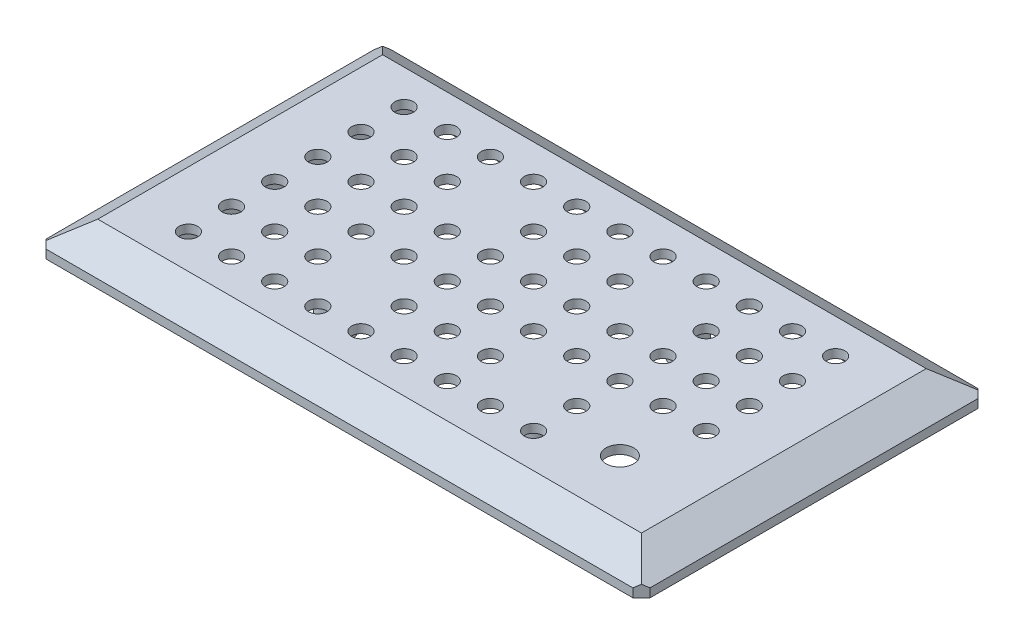
SolidWorks part; units mm, degrees
other "Markierung1"
sketch "Skizze3" plane through (70, 7.0001, 40) normal (0.1525, 0.9868, 0.0548) x (-0.3361, 0.104, -0.9361)
ref_plane "Front Plane" through (0, 0, 0) normal (0, 0, 1) x (1, 0, 0)
ref_plane "Top Plane" through (0, 0, 0) normal (0, 1, 0) x (1, 0, 0)
ref_plane "Right Plane" through (0, 0, 0) normal (1, 0, 0) x (0, 0, -1)
sketch "Sketch1" plane through (0, 0, 0) normal (0, 1, 0) x (1, 0, 0)
  line L1 (-70, -40) -> (70, -40)
  line L2 (-70, -40) -> (-70, 40)
  line L3 (-70, 40) -> (70, 40)
  line L4 (70, -40) -> (70, 40)
  line L5 (-70, -40) -> (70, 40) construction
  line L6 (-70, 40) -> (70, -40) construction
  point P0 (0, 0)
  dimension "D1" = 140
  dimension "D2" = 80
extrude "Boss-Extrude1" add sketch "Sketch1" along normal blind 2
sketch "Sketch2" plane through (0, 2, 0) normal (0, 1, 0) x (1, 0, 0)
  line L4 (70, -40) -> (70, 40)
  line L5 (70, 40) -> (-70, 40)
  line L6 (-70, 40) -> (-70, -40)
  line L7 (-70, -40) -> (70, -40)
  line L8 (70, -40) -> (70, 40)
  line L9 (70, 40) -> (-70, 40)
  line L10 (-70, 40) -> (-70, -40)
  line L11 (-70, -40) -> (70, -40)
  dimension "D1" = 0
ref_plane "Plane1" through (0, 7, 0) normal (0, 1, 0) x (1, 0, 0)
sketch "Sketch3" plane through (0, 7, 0) normal (0, 1, 0) x (1, 0, 0)
  line L0 (-70, 40) -> (-70, -40) construction
  line L1 (-63, -33) -> (63, -33)
  line L2 (-63, -33) -> (-63, 33)
  line L3 (-63, 33) -> (63, 33)
  line L4 (63, -33) -> (63, 33)
  line L5 (-63, -33) -> (63, 33) construction
  line L6 (-63, 33) -> (63, -33) construction
  line L7 (70, 40) -> (-70, 40) construction
  point P0 (0, 0)
  dimension "D1" = 7
  dimension "D2" = 7
loft "Loft1" add profiles "Sketch3", "Sketch2" connector at (-63, 7, 33) connector at (-70, 2, 40)
chamfer "Chamfer2" distance 2 angle 45 4 edges at (70, 1, 40) (70, 1, -40) (-70, 1, -40) (-70, 1, 40)
sketch "Sketch4" plane through (0, 0, 0) normal (0, -1, 0) x (1, 0, 0)
  line L0 (-70, -38) -> (-70, 38) construction
  line L1 (-62.9, 15) -> (-54.9, 15)
  line L2 (-62.9, 15) -> (-62.9, 25)
  line L3 (-62.9, 25) -> (-54.9, 25)
  line L4 (-54.9, 15) -> (-54.9, 25)
  line L5 (-62.9, 15) -> (-54.9, 25) construction
  line L6 (-62.9, 25) -> (-54.9, 15) construction
  line L7 (-70, 0) -> (70, 0) construction
  line L8 (70, 38) -> (70, -38) construction
  line L9 (0, 40) -> (0, -40) construction
  line L10 (-68, 40) -> (68, 40) construction
  line L11 (68, -40) -> (-68, -40) construction
  line L12 (-62.9, -25) -> (-54.9, -15) construction
  line L13 (-62.9, -15) -> (-54.9, -25) construction
  line L14 (-54.9, -15) -> (-54.9, -25)
  line L15 (-62.9, -25) -> (-54.9, -25)
  line L16 (-62.9, -15) -> (-62.9, -25)
  line L17 (-62.9, -15) -> (-54.9, -15)
  line L18 (62.9, -15) -> (54.9, -25) construction
  line L19 (62.9, -25) -> (54.9, -15) construction
  line L20 (62.9, 25) -> (54.9, 15) construction
  line L21 (62.9, 15) -> (54.9, 25) construction
  line L22 (62.9, -15) -> (54.9, -15)
  line L23 (62.9, -15) -> (62.9, -25)
  line L24 (62.9, -25) -> (54.9, -25)
  line L25 (54.9, -15) -> (54.9, -25)
  line L26 (54.9, 15) -> (54.9, 25)
  line L27 (62.9, 25) -> (54.9, 25)
  line L28 (62.9, 15) -> (62.9, 25)
  line L29 (62.9, 15) -> (54.9, 15)
  point P0 (-58.9, 20)
  point P21 (-58.9, -20)
  point P30 (58.9, -20)
  point P31 (58.9, 20)
  dimension "D1" = 10
  dimension "D2" = 7.1
  dimension "D3" = 8
  dimension "D4" = 40
extrude "Boss-Extrude2" add sketch "Sketch4" along normal blind 7
sketch "Sketch5" plane through (-62.9, 0, 0) normal (-1, 0, 0) x (0, 0, 1)
  line L0 (-15, 0) -> (-25, -7) construction
  line L1 (0, 0) -> (0, 50000) construction
  circle A0 centre (-20, -3.5) radius 2.05
  circle A1 centre (20, -3.5) radius 2.05
  dimension "D1" = 4.1
extrude "Cut-Extrude1" cut sketch "Sketch5" against normal through all
sketch "Sketch6" plane through (0, 0, 0) normal (0, -1, 0) x (1, 0, 0)
  line L0 (54.9, 25) -> (54.9, 15) construction
  line L1 (-53.9, -32) -> (53.9, -32)
  line L2 (-53.9, -32) -> (-53.9, 32)
  line L3 (-53.9, 32) -> (53.9, 32)
  line L4 (53.9, -32) -> (53.9, 32)
  line L5 (-53.9, -32) -> (53.9, 32) construction
  line L6 (-53.9, 32) -> (53.9, -32) construction
  line L8 (-63, 33) -> (63, 33) construction
  point P0 (0, 0)
  dimension "D1" = 1
  dimension "D2" = 1
extrude "Cut-Extrude2" cut sketch "Sketch6" against normal offset from surface (5 mm away) 2 up to face at (0, 7, 0)
sketch "Skizze1" plane through (0, 7, 0) normal (0, 1, 0) x (1, 0, 0)
  line L0 (-53.9, 0) -> (53.9, 0) construction
  line L1 (0, -32) -> (0, 32) construction
  line L2 (-50, -25) -> (50, 25) construction
  line L4 (63, -33) -> (63, 33)
  line L5 (63, 33) -> (-63, 33)
  line L6 (-63, 33) -> (-63, -33)
  line L7 (-63, -33) -> (63, -33)
  line L8 (63, -33) -> (63, 33) construction
  line L9 (63, 33) -> (-63, 33) construction
  line L10 (-63, 33) -> (-63, -33) construction
  line L11 (-63, -33) -> (63, -33) construction
  line L12 (53.9, -32) -> (53.9, 32)
  line L13 (-53.9, -32) -> (53.9, -32)
  line L14 (-53.9, 32) -> (-53.9, -32)
  line L15 (53.9, 32) -> (-53.9, 32)
  line L16 (53.9, -32) -> (53.9, 32) construction
  line L17 (-53.9, -32) -> (53.9, -32) construction
  line L18 (-53.9, 32) -> (-53.9, -32) construction
  line L19 (53.9, 32) -> (-53.9, 32) construction
  circle A0 centre (-50, -25) radius 2.15
  circle A1 centre (-40, -25) radius 2.15
  circle A2 centre (-30, -25) radius 2.15
  circle A3 centre (-20, -25) radius 2.15
  circle A4 centre (-10, -25) radius 2.15
  circle A5 centre (0, -25) radius 2.15
  circle A6 centre (10, -25) radius 2.15
  circle A7 centre (20, -25) radius 2.15
  circle A8 centre (30, -25) radius 2.15
  circle A9 centre (40, -25) radius 2.15
  circle A10 centre (50, -25) radius 2.15
  circle A11 centre (-40, -15) radius 2.15
  circle A12 centre (-30, -15) radius 2.15
  circle A13 centre (-20, -15) radius 2.15
  circle A14 centre (-10, -15) radius 2.15
  circle A15 centre (0, -15) radius 2.15
  circle A16 centre (10, -15) radius 2.15
  circle A17 centre (20, -15) radius 2.15
  circle A18 centre (30, -15) radius 2.15
  circle A19 centre (40, -15) radius 2.15
  circle A20 centre (50, -15) radius 2.15
  circle A21 centre (-40, -5) radius 2.15
  circle A22 centre (-30, -5) radius 2.15
  circle A23 centre (-20, -5) radius 2.15
  circle A24 centre (-10, -5) radius 2.15
  circle A25 centre (0, -5) radius 2.15
  circle A26 centre (10, -5) radius 2.15
  circle A27 centre (20, -5) radius 2.15
  circle A28 centre (30, -5) radius 2.15
  circle A29 centre (40, -5) radius 2.15
  circle A30 centre (50, -5) radius 2.15
  circle A31 centre (-40, 5) radius 2.15
  circle A32 centre (-30, 5) radius 2.15
  circle A33 centre (-20, 5) radius 2.15
  circle A34 centre (-10, 5) radius 2.15
  circle A35 centre (0, 5) radius 2.15
  circle A36 centre (10, 5) radius 2.15
  circle A37 centre (20, 5) radius 2.15
  circle A38 centre (30, 5) radius 2.15
  circle A39 centre (40, 5) radius 2.15
  circle A40 centre (50, 5) radius 2.15
  circle A41 centre (-40, 15) radius 2.15
  circle A42 centre (-30, 15) radius 2.15
  circle A43 centre (-20, 15) radius 2.15
  circle A44 centre (-10, 15) radius 2.15
  circle A45 centre (0, 15) radius 2.15
  circle A46 centre (10, 15) radius 2.15
  circle A47 centre (20, 15) radius 2.15
  circle A48 centre (30, 15) radius 2.15
  circle A49 centre (40, 15) radius 2.15
  circle A50 centre (50, 15) radius 2.15
  circle A51 centre (-40, 25) radius 2.15
  circle A52 centre (-30, 25) radius 2.15
  circle A53 centre (-20, 25) radius 2.15
  circle A54 centre (-10, 25) radius 2.15
  circle A55 centre (0, 25) radius 2.15
  circle A56 centre (10, 25) radius 2.15
  circle A57 centre (20, 25) radius 2.15
  circle A58 centre (30, 25) radius 2.15
  circle A59 centre (40, 25) radius 2.15
  circle A60 centre (50, 25) radius 2.15
  circle A61 centre (-50, -15) radius 2.15
  circle A62 centre (-50, -5) radius 2.15
  circle A63 centre (-50, 5) radius 2.15
  circle A64 centre (-50, 15) radius 2.15
  circle A65 centre (-50, 25) radius 2.15
  point P14 (0, 0)
  point P15 (0, 0)
  point P16 (0, 0)
  point P18 (0, 0)
  dimension "D3" = 11
  dimension "D5" = 4.3
  dimension "D1" = 0
  dimension "D2" = 0
  dimension "D4" = 6
extrude "Schnitt-Linear austragen2" cut sketch "Skizze1" against normal blind 10
sketch "Skizze2" plane through (0, 7, 0) normal (0, 1, 0) x (1, 0, 0)
  line L1 (37.85, -27.15) -> (52.15, -27.15)
  line L2 (37.85, -27.15) -> (37.85, -12.85)
  line L3 (37.85, -12.85) -> (52.15, -12.85)
  line L4 (52.15, -27.15) -> (52.15, -12.85)
  line L5 (37.85, -27.15) -> (52.15, -12.85) construction
  line L6 (37.85, -12.85) -> (52.15, -27.15) construction
  circle A0 centre (40, -25) radius 2.15 construction
  circle A1 centre (50, -25) radius 2.15 construction
  circle A2 centre (50, -15) radius 2.15 construction
  circle A3 centre (45, -20) radius 3.2
  point P0 (45, -20)
  dimension "D1" = 6.4
extrude "Aufsatz-Linear austragen1" add sketch "Skizze2" against normal up to surface (2 mm away) up to face at (-20, 5, -7.15)
extrude "Schnitt-Linear austragen4" cut sketch "Skizze2<4>" against normal blind 10 contours A3
sketch "Skizze2<4>" plane through (0, 7, 0) normal (0, 1, 0) x (1, 0, 0) same geometry as "Skizze2"
sketch "Skizze5" plane through (0, 7, 0) normal (0, 1, 0) x (1, 0, 0)
  circle A0 centre (20, -15) radius 2.15 construction
  circle A1 centre (20, 15) radius 2.15 construction
  circle A2 centre (-20, 15) radius 2.15 construction
  circle A3 centre (20, -15) radius 2.15
  circle A4 centre (20, 15) radius 2.15
  circle A5 centre (-20, 15) radius 2.15
  circle A6 centre (-20, -15) radius 2.15 construction
  circle A7 centre (-20, -15) radius 2.15
extrude "Aufsatz-Linear austragen2" add sketch "Skizze5" against normal up to surface (2 mm away) up to face at (45, 5, 16.8)
sketch "Skizze4" plane through (0, 7, 0) normal (0, 1, 0) x (1, 0, 0)
  line L1 (-23.105, -17.725) -> (23.105, -17.725) construction
  line L2 (-23.105, -17.725) -> (-23.105, 17.725) construction
  line L3 (-23.105, 17.725) -> (23.105, 17.725) construction
  line L4 (23.105, -17.725) -> (23.105, 17.725) construction
  line L5 (-23.105, -17.725) -> (23.105, 17.725) construction
  line L6 (-23.105, 17.725) -> (23.105, -17.725) construction
  circle A0 centre (-23.105, -17.725) radius 2.05
  circle A1 centre (-23.105, 17.725) radius 2.05
  circle A2 centre (23.105, 17.725) radius 2.05
  circle A3 centre (23.105, -17.725) radius 2.05
  circle A4 centre (-23.105, 17.725) radius 3.65
  circle A5 centre (23.105, 17.725) radius 3.65
  circle A6 centre (23.105, -17.725) radius 3.65
  circle A7 centre (-23.105, -17.725) radius 3.65
  point P0 (0, 0)
  point P1 (0, 0)
  dimension "D3" = 4.1
  dimension "D4" = 1.6
  dimension "D1" = 35.45
  dimension "D2" = 46.21
extrude "Aufsatz-Linear austragen3" add sketch "Skizze4" against normal blind 10 contours A5 | A2 | A4 | A1 | A6 | A3 | A7 | A0
